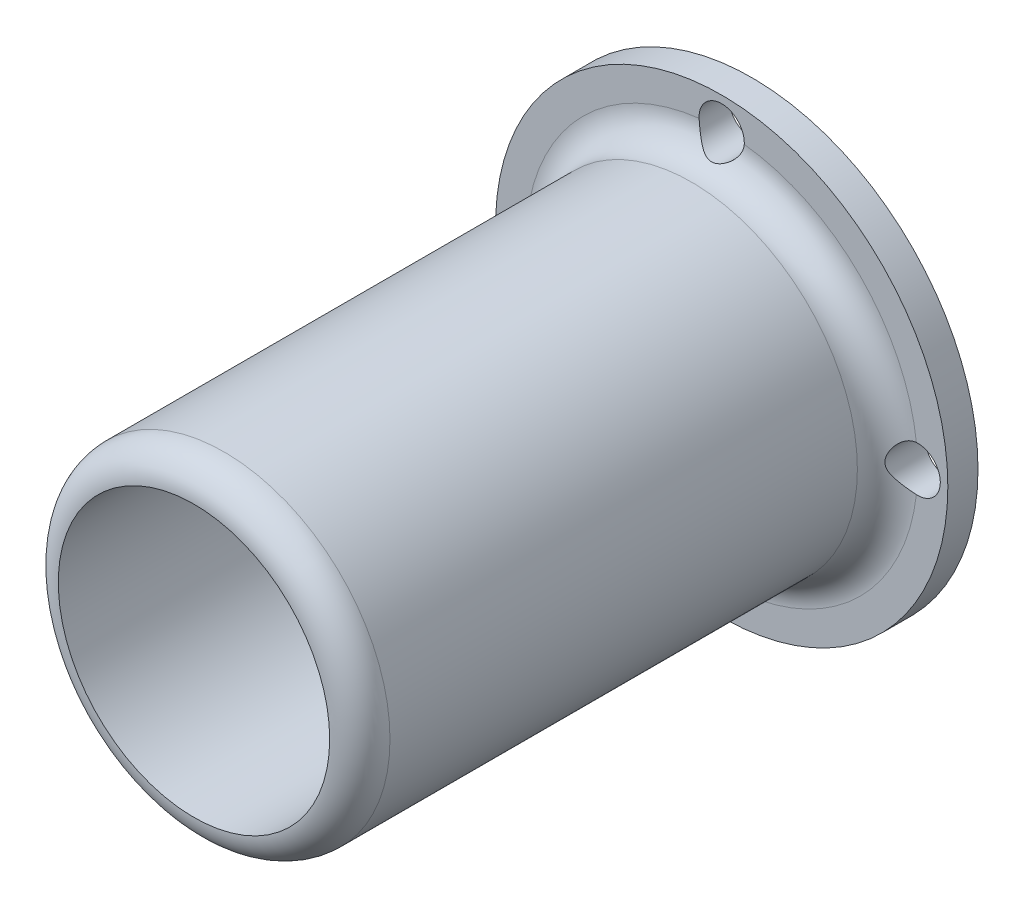
SolidWorks part; units mm, degrees
ref_plane "Front Plane" through (0, 0, 0) normal (0, 0, 1) x (1, 0, 0)
ref_plane "Top Plane" through (0, 0, 0) normal (0, 1, 0) x (1, 0, 0)
ref_plane "Right Plane" through (0, 0, 0) normal (1, 0, 0) x (0, 0, -1)
sketch "Sketch1" plane through (0, 0, 0) normal (0, 0, 1) x (1, 0, 0)
  circle A0 centre (0, 0) radius 15
  dimension "D1" = 30
extrude "Boss-Extrude1" add sketch "Sketch1" along normal blind 2
sketch "Sketch2" plane through (0, 0, 2) normal (0, 0, 1) x (1, 0, 0)
  circle A0 centre (0, 0) radius 11
  circle A1 centre (0, 0) radius 9
  dimension "D1" = 22
  dimension "D2" = 18
extrude "Boss-Extrude2" add sketch "Sketch2" along normal blind 35
sketch "Sketch3" plane through (0, 0, 2) normal (0, 0, 1) x (1, 0, 0)
  line L0 (0, 0) -> (-13, 0) construction
  line L1 (0, 13) -> (0, 0) construction
  circle A0 centre (0, 0) radius 13 construction
  circle A1 centre (0, 13) radius 1.5
  circle A2 centre (13, 0) radius 1.5
  circle A3 centre (0, -13) radius 1.5
  circle A4 centre (-13, 0) radius 1.5
  point P5 (0, 0)
  point P6 (0, 0)
  point P14 (0, 0)
  dimension "D1" = 26
  dimension "D2" = 3
  dimension "D3" = 4
extrude "Cut-Extrude1" cut sketch "Sketch3" against normal through all
fillet "Fillet1" radius 2 2 edges at (11, 0, 2) (11, 0, 37)
fillet "Fillet2" radius 2 1 edges at (9, 0, 2)
